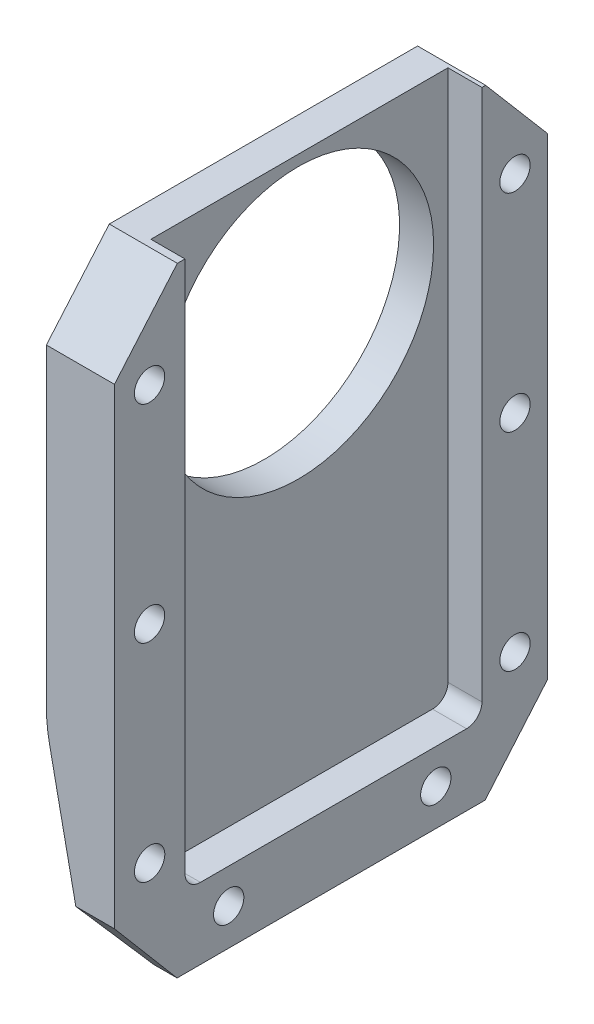
SolidWorks part; units mm, degrees
material "PLA"
ref_plane "Front Plane" through (0, 0, 0) normal (0, 0, 1) x (1, 0, 0)
ref_plane "Top Plane" through (0, 0, 0) normal (0, 1, 0) x (1, 0, 0)
ref_plane "Right Plane" through (0, 0, 0) normal (1, 0, 0) x (0, 0, -1)
sketch "Sketch1" plane through (0, 0, 0) normal (0, 0, 1) x (1, 0, 0)
  line L0 (0, 0) -> (0, 50.8)
  line L1 (0, 50.8) -> (-5.588, 50.8)
  line L2 (-5.588, 50.8) -> (-5.588, 17.78)
  line L3 (-5.588, 17.78) -> (-1.9166, 0)
  line L4 (-1.9166, 0) -> (0, 0)
extrude "Boss-Extrude1" add sketch "Sketch1" along normal blind 35.56
fillet "Fillet1" radius 12.7 1 edges at (-5.588, 17.78, 17.78)
sketch "Sketch6" plane through (0, 0, 0) normal (1, 0, 0) x (0, 0, -1)
  line L0 (-17.78, 50.8) -> (-17.78, 0) construction
  line L1 (-35.56, 50.8) -> (0, 50.8) construction
  line L2 (-35.56, 0) -> (0, 0) construction
  line L4 (-29.772, 50.8) -> (-5.388, 50.8)
  line L5 (-29.772, 50.8) -> (-29.772, 5.842)
  line L6 (-29.772, 5.842) -> (-5.388, 5.842)
  line L7 (-5.388, 50.8) -> (-5.388, 5.842)
  dimension "D1" = 44.958
  dimension "D2" = 24.384
extrude "Cut-Extrude1" cut sketch "Sketch6" against normal blind 2.794
fillet "Fillet2" radius 1.27 2 edges at (-1.397, 5.842, 29.772) (-1.397, 5.842, 5.388)
sketch "Sketch10" plane through (0, 0, 0) normal (1, 0, 0) x (0, 0, -1)
  line L0 (-35.56, 44.7804) -> (-30.3976, 50.8)
  line L1 (-35.56, 0) -> (-35.56, 50.8) construction
  line L2 (-35.56, 50.8) -> (-29.772, 50.8) construction
  line L3 (-30.3976, 50.8) -> (-35.56, 50.8)
  line L4 (-35.56, 50.8) -> (-35.56, 44.7804)
extrude "Cut-Extrude3" cut sketch "Sketch10" against normal through all
sketch "Sketch11" plane through (0, 0, 0) normal (1, 0, 0) x (0, 0, -1)
  line L0 (-5.0855, 50.8) -> (0, 50.8)
  line L1 (-5.388, 50.8) -> (0, 50.8) construction
  line L2 (0, 50.8) -> (0, 44.8249)
  line L3 (0, 0) -> (0, 50.8) construction
  line L4 (0, 44.8249) -> (-5.0855, 50.8)
  line L5 (0, 6.0295) -> (-5.1287, 0)
  line L6 (-35.56, 0) -> (0, 0) construction
  line L7 (-5.1287, 0) -> (0, 0)
  line L8 (0, 0) -> (0, 6.0295)
  line L9 (-35.56, 6.0712) -> (-35.56, 0)
  line L10 (-35.56, 0) -> (-35.56, 44.7804) construction
  line L11 (-35.56, 0) -> (-30.4171, 0)
  line L12 (-30.4171, 0) -> (-35.56, 6.0712)
extrude "Cut-Extrude4" cut sketch "Sketch11" against normal through all
hole_wizard "7/8 (0.875) Diameter Hole1" positions "Sketch12" profile "Sketch13" hole size "7/8" standard "ANSI Inch" end condition through all
sketch "Sketch12" plane through (-5.588, 0, 0) normal (-1, 0, 0) x (0, 0, 1)
  point P0 (17.6785, 38.8095)
sketch "Sketch13" plane through (-5.588, 38.8095, 17.6785) normal (0, 1, 0) x (0, 0, 1)
  line L0 (0, 0) -> (0, 5.588)
  line L1 (0, 5.588) -> (11.1125, 5.588)
  line L2 (11.1125, 5.588) -> (11.1125, 0)
  line L5 (11.1125, 0) -> (0, 0)
  line L11 (0, -6.35) -> (0, 107.95) construction
  dimension "Thru Hole Dia." = 22.225
  dimension "Thru Hole Depth" = 5.588
hole_wizard "#40 (0.098) Diameter Hole1" positions "Sketch14" profile "Sketch15" hole size "#40" standard "ANSI Inch" end condition through all
sketch "Sketch14" plane through (-5.588, 0, 0) normal (-1, 0, 0) x (0, 0, 1)
  point P0 (2.6785, 43.3095)
  point P3 (2.6785, 26.3095)
  point P6 (2.6785, 9.3095)
  point P9 (9.1785, 3.0095)
  point P12 (26.1819, 2.9992)
  point P14 (32.6729, 9.2992)
  point P16 (32.6785, 26.3095)
  point P19 (32.6785, 43.2992)
sketch "Sketch15" plane through (-5.588, 43.3095, 2.6785) normal (0, 1, 0) x (0, 0, 1)
  line L0 (0, 0) -> (0, 5.588)
  line L1 (0, 5.588) -> (1.2446, 5.588)
  line L2 (1.2446, 5.588) -> (1.2446, 0.635)
  line L3 (1.2446, 0.635) -> (1.8796, 0)
  line L5 (1.8796, 0) -> (0, 0)
  line L6 (-1.2446, 0.635) -> (-1.8796, 0) construction
  line L11 (0, -6.35) -> (0, 107.95) construction
  dimension "Thru Hole Dia." = 2.4892
  dimension "Thru Hole Depth" = 5.588
  dimension "Near C'Sink Dia." = 3.7592
  dimension "Near C'Sink Angle" = 90
sketch "Sketch17" plane through (-5.588, 0, 0) normal (-1, 0, 0) x (0, 0, 1)
  line L0 (6.566, 38.8095) -> (28.791, 38.8095) construction
  circle A0 centre (17.6785, 38.8095) radius 11.1125 construction
  circle A1 centre (17.6785, 38.8095) radius 11.1125
  point P7 (17.6785, 38.8095)
